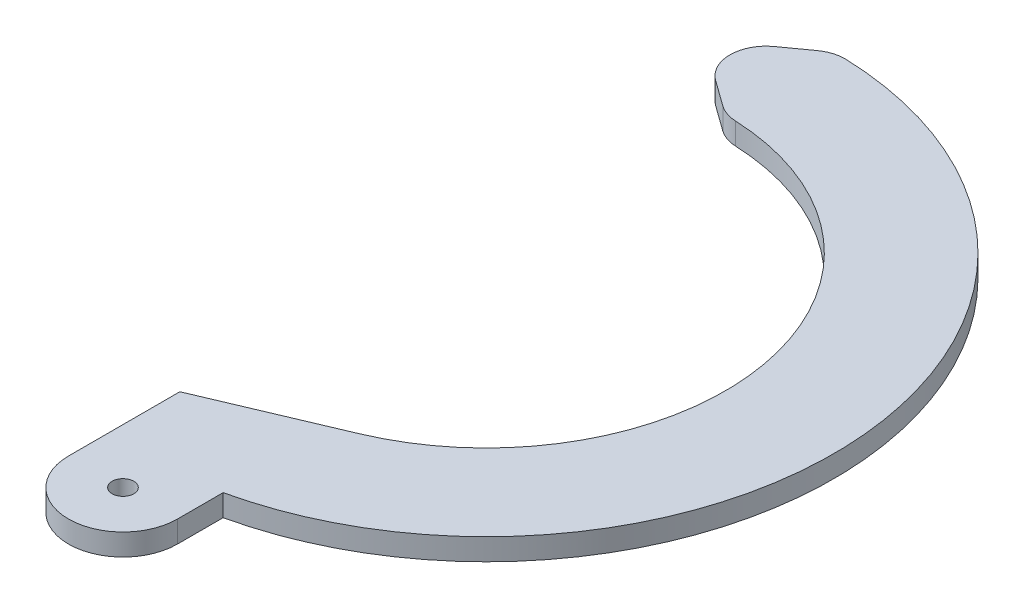
SolidWorks part; units mm, degrees
ref_plane "Front Plane" through (0, 0, 0) normal (0, 0, 1) x (1, 0, 0)
ref_plane "Top Plane" through (0, 0, 0) normal (0, 1, 0) x (1, 0, 0)
ref_plane "Right Plane" through (0, 0, 0) normal (1, 0, 0) x (0, 0, -1)
sketch "Sketch1" plane through (0, 0, 0) normal (0, 1, 0) x (1, 0, 0)
  line L0 (0, 0) -> (0, -48)
  line L1 (0, 0) -> (0, 33)
  line L2 (0, -48) -> (0, -53.14)
  line L3 (-4.5537, -53.14) -> (10.5, -53.14)
  line L6 (-4.5537, -53.14) -> (-4.5537, -32.6843)
  line L7 (10.5, -53.14) -> (10.5, -31.285)
  line L8 (0, 33) -> (0, 48)
  line L9 (0, 40.5) -> (-10.4222, 40.5) construction
  line L10 (0, 33) -> (-10.4222, 40.5)
  line L11 (-10.4222, 40.5) -> (0, 48)
  circle A4 centre (0, 0) radius 33
  circle A5 centre (0, 0) radius 48
  circle A8 centre (2.9732, -53.14) radius 1.5
  arc A9 (-4.5537, -53.14) -> (10.5, -53.14) centre (2.9732, -53.14) ccw
  dimension "D1" = 66
  dimension "D2" = 15
  dimension "D4" = 3
  dimension "D3" = 5.14
extrude "Boss-Extrude2" add sketch "Sketch1" along normal blind 3 contours A8 | A8 L7 A5 L2 | A5 L6 L2 | L6 A5 L0 A4 | L0 A5 L7 A4 | L7 A5 L8 A4 | L8 L9 L10 | L9 L8 L11 region at (5.2815, 0, 40.0198) region at (-2.2793, 0, 40.4113) region at (-3.4741, 0, -38) region at (1.0629, 0, -36.75) region at (5.5932, 0, 50.2277) region at (-2.2926, 0, 50.5336) region at (-3.4741, 0, -43) region at (2.9732, 0, 56.4403)
fillet "Fillet1" radius 5 1 edges at (-10.4222, 1.5, -40.5)
fillet "Fillet2" radius 5 2 edges at (0, 1.5, -48) (0, 1.5, -33)
sketch "Sketch4" plane through (0, 3, 0) normal (0, 1, 0) x (1, 0, 0)
  line L0 (2.9732, -53.14) -> (2.9732, -32.8658) construction
  line L1 (12.8942, -30.3766) -> (-4.5537, -37.7601)
  line L2 (-4.5537, -53.14) -> (-4.5537, -32.6843) construction
  line L3 (-4.5537, -37.7601) -> (-8.4005, -23.1788)
  line L4 (-8.4005, -23.1788) -> (12.8942, -30.3766)
  arc A0 (-4.5537, -32.6843) -> (1.4438, 32.9684) centre (0, 0) ccw construction
extrude "Cut-Extrude1" cut sketch "Sketch4" against normal blind 3
